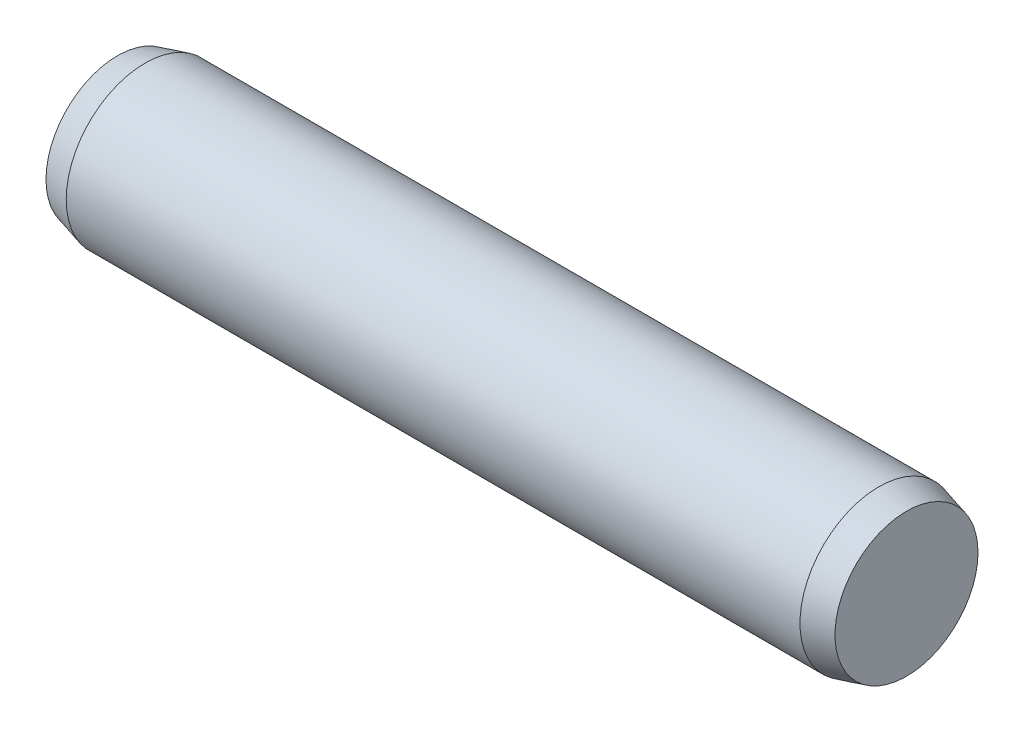
SolidWorks part; units mm, degrees
ref_plane "Front Plane" through (0, 0, 0) normal (0, 0, 1) x (1, 0, 0)
ref_plane "Top Plane" through (0, 0, 0) normal (0, 1, 0) x (1, 0, 0)
ref_plane "Right Plane" through (0, 0, 0) normal (1, 0, 0) x (0, 0, -1)
sketch "Sketch1" plane through (0, 0, 0) normal (0, 0, 1) x (1, 0, 0)
  line L0 (-4.65, 0) -> (4.65, 0) construction
  line L1 (4.65, 1) -> (4.65, -1) construction
  line L2 (-4.65, 1) -> (-4.65, -1) construction
  line L3 (5, 1) -> (5, -1) construction
  line L4 (-5, 1) -> (-5, -1) construction
  line L5 (-4.65, 0) -> (-5, 0) construction
  line L6 (4.65, 0) -> (5, 0) construction
  dimension "D1" = 0.35
  dimension "Dia" = 2
  dimension "Length" = 10
  dimension "C" = 0.35
sketch "Sketch2" plane through (0, 0, 0) normal (1, 0, 0) x (0, 0, -1)
  circle A0 centre (0, 0) radius 1
extrude "Extrude1" add sketch "Sketch2" against normal up to vertex (4.65 mm away) and the other way up to vertex (4.65 mm away) up to point (-4.65, 1, 0) other way up to point (4.65, 1, 0)
sketch "Sketch3" plane through (4.65, 0, 0) normal (1, 0, 0) x (0, 0, -1)
  circle A1 centre (0, 0) radius 1
  circle A2 centre (0, 0) radius 1
  dimension "D1" = 0
extrude "Extrude2" add sketch "Sketch3" along normal up to vertex (0.35 mm away) draft 15 up to point (5, 0, 0)
sketch "Sketch4" plane through (-4.65, 0, 0) normal (-1, 0, 0) x (0, 0, 1)
  circle A1 centre (0, 0) radius 1
  circle A2 centre (0, 0) radius 1
  dimension "D1" = 0
extrude "Extrude3" add sketch "Sketch4" along normal up to vertex (0.35 mm away) draft 15 up to point (-5, 0, 0)
equation "\"D1@Sketch1\" = \"C@Sketch1\""
